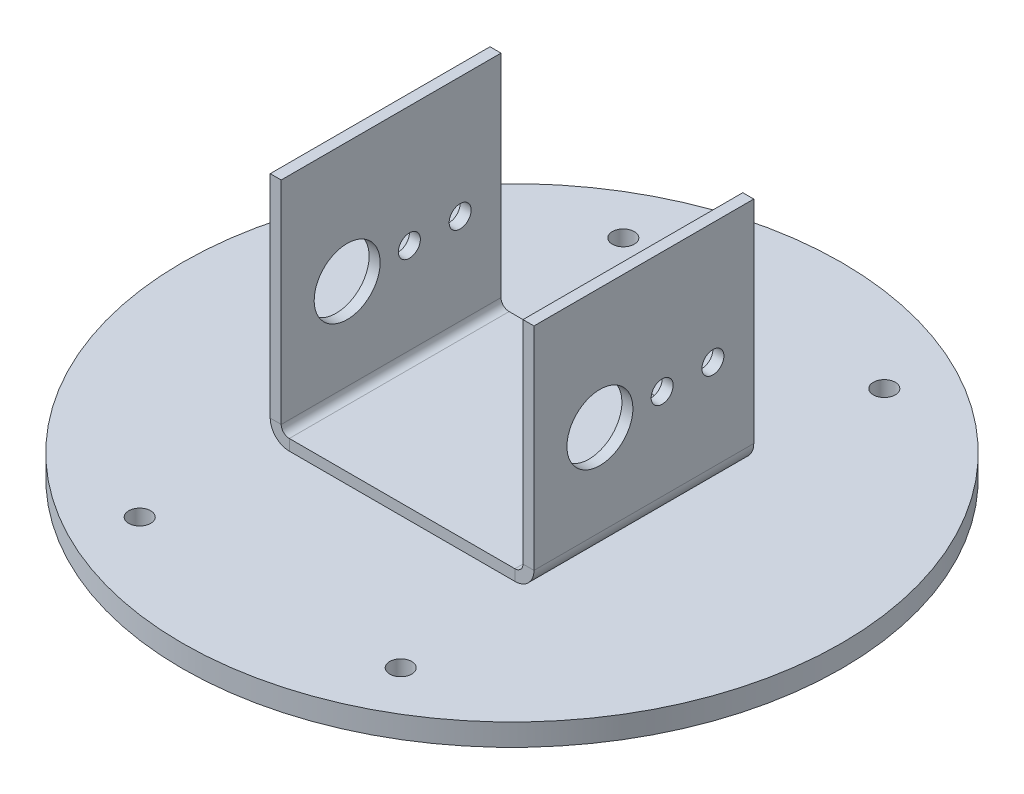
SolidWorks part; units mm, degrees
note: The reader was unsure of these and kept them because the rebuilt part matched: flange length of "Edge-Flange1".
ref_plane "Front Plane" through (0, 0, 0) normal (0, 0, 1) x (1, 0, 0)
ref_plane "Top Plane" through (0, 0, 0) normal (0, 1, 0) x (1, 0, 0)
ref_plane "Right Plane" through (0, 0, 0) normal (1, 0, 0) x (0, 0, -1)
sketch "Sketch3" plane through (0, 0, 0) normal (0, 1, 0) x (1, 0, 0)
  line L1 (11.8743, -22) -> (-11.8743, -22) construction
  line L2 (11.8743, -22) -> (11.8743, 22) construction
  line L3 (11.8743, 22) -> (-11.8743, 22) construction
  line L4 (-11.8743, -22) -> (-11.8743, 22) construction
  line L5 (11.8743, -22) -> (-11.8743, 22) construction
  line L6 (11.8743, 22) -> (-11.8743, -22) construction
  circle A0 centre (0, 0) radius 30
  circle A1 centre (-11.8743, 22) radius 1
  circle A2 centre (11.8743, 22) radius 1
  circle A3 centre (11.8743, -22) radius 1
  circle A4 centre (-11.8743, -22) radius 1
  dimension "D1" = 60
  dimension "D4" = 2
  dimension "D2" = 50
  dimension "D3" = 44
extrude "Boss-Extrude1" add sketch "Sketch3" along normal blind 2
sketch "Sketch4" plane through (0, 2, 0) normal (0, 1, 0) x (1, 0, 0)
  line L1 (-11, 10) -> (11, 10)
  line L2 (-11, 10) -> (-11, -10)
  line L3 (-11, -10) -> (11, -10)
  line L4 (11, 10) -> (11, -10)
  line L5 (-11, 10) -> (11, -10) construction
  line L6 (-11, -10) -> (11, 10) construction
  point P0 (0, 0)
  dimension "D1" = 22
  dimension "D2" = 20
base flange "Base-Flange1" sketch "Sketch4" thickness 1 reverse thickness direction yes parameters "D1"=0.7366
edge flange "Edge-Flange1" sketch "Sketch15" flange profiles "Sketch15", "Sketch16" flange angle 90 flange length 20 flange position material outside bend radius 0.7366 thickness 1 relief rectangular parameters "D6"=10, "D8"=1
sketch "Sketch15" plane through (-11, 3, 0) normal (-1, 0, 0) x (0, 0, 1)
  line L0 (-10, 0) -> (10, 0) construction
  line L1 (-10, 0) -> (10, 0)
  line L2 (-10, 0) -> (-10, 20)
  line L3 (-10, 20) -> (10, 20)
  line L4 (10, 20) -> (10, 0)
sketch "Sketch16" plane through (11, 3, 0) normal (1, 0, 0) x (0, 0, -1)
  line L0 (-10, 0) -> (10, 0) construction
  line L1 (-10, 0) -> (10, 0)
  line L2 (-10, 0) -> (-10, 20)
  line L3 (-10, 20) -> (10, 20)
  line L4 (10, 20) -> (10, 0)
bend "EdgeBend1" bend radius 0.7366 bend angle 90 parameters "D5"=1
bend "EdgeBend2" bend radius 0.7366 bend angle 90 parameters "D5"=2
sketch "Sketch17" plane through (0, 0, 0) normal (1, 0, 0) x (0, 0, -1)
  line L0 (10, 3) -> (-10, 3) construction
  line L1 (-10, 23) -> (-10, 3.7366) construction
  circle A0 centre (-4, 12) radius 3
  circle A1 centre (1.6622, 12) radius 1
  circle A2 centre (6.2806, 12) radius 1
  dimension "D3" = 6
  dimension "D4" = 2
  dimension "D1" = 9
  dimension "D2" = 6
extrude "Cut-Extrude1" cut sketch "Sketch17" against normal through all both and the other way through all
sketch "Bend-Lines1" [suppressed] plane through (0, 0, 0) normal (0, 1, 0) x (1, 0, 0)
sketch "Bounding-Box1" [suppressed] plane through (0, 0, 0) normal (0, 1, 0) x (1, 0, 0)
sheet metal parameters "Sheet-Metal2" thickness 1 parameters "D1"=0.7366
flat pattern "Flat-Pattern2" [suppressed]
sketch "Bend-Lines2" plane through (0, 0, 0) normal (0, 1, 0) x (1, 0, 0)
sketch3d "Bounding-Box2" [suppressed]
  line L0 (11, -7.5, 0) -> (-11, -7.5, 0) construction
  line L1 (11, 7.5, 0) -> (-11, 7.5, 0) construction
  line L2 (11, -7.5, 0) -> (11, 7.5, 0) construction
  line L3 (-11, -7.5, 0) -> (-11, 7.5, 0) construction
sheet metal parameters "Sheet-Metal3" thickness 1 parameters "D1"=0.7366
flat pattern "Flat-Pattern2"
sketch "Bend-Lines2" plane through (0, 2, 0) normal (0, -1, 0) x (-1, 0, 0)
  line L0 (-11.2346, 10) -> (-11.2346, -10) construction
  line L1 (11.2346, -10) -> (11.2346, 10) construction
  line L2 (-11.2346, 10) -> (-11.2346, -10) construction
  line L3 (11.2346, -10) -> (11.2346, 10) construction
sketch3d "Bounding-Box2" [suppressed]
  line L0 (-31.4692, -10, 0) -> (31.4692, -10, 0) construction
  line L1 (-31.4692, 10, 0) -> (31.4692, 10, 0) construction
  line L2 (-31.4692, -10, 0) -> (-31.4692, 10, 0) construction
  line L3 (31.4692, -10, 0) -> (31.4692, 10, 0) construction
bend of the flat pattern "Flatten-<EdgeBend1>1"
bend of the flat pattern "Flatten-<EdgeBend2>1"
sheet metal parameters "Sheet-Metal4" thickness 1 parameters "D1"=0.7366
flat pattern "Flat-Pattern2"
sketch "Bend-Lines2" plane through (0, 2, 0) normal (0, -1, 0) x (-1, 0, 0)
  line L0 (-11.2346, 10) -> (-11.2346, -10) construction
  line L1 (11.2346, -10) -> (11.2346, 10) construction
  line L2 (-11.2346, 10) -> (-11.2346, -10) construction
  line L3 (11.2346, -10) -> (11.2346, 10) construction
sketch3d "Bounding-Box2" [suppressed]
  line L0 (-31.4692, -10, 0) -> (31.4692, -10, 0) construction
  line L1 (-31.4692, 10, 0) -> (31.4692, 10, 0) construction
  line L2 (-31.4692, -10, 0) -> (-31.4692, 10, 0) construction
  line L3 (31.4692, -10, 0) -> (31.4692, 10, 0) construction
bend of the flat pattern "Flatten-<EdgeBend1>1"
bend of the flat pattern "Flatten-<EdgeBend2>1"
